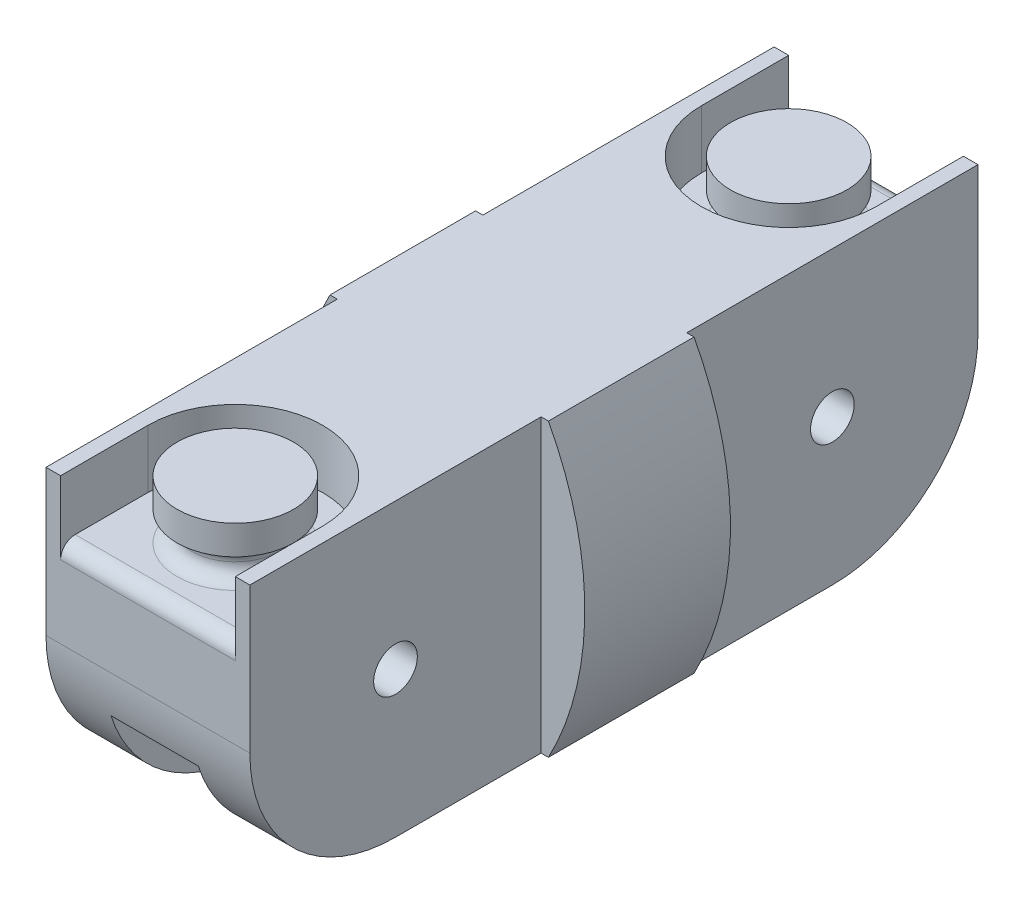
SolidWorks part; units mm, degrees
ref_plane "Alzado" through (0, 0, 0) normal (0, 0, 1) x (1, 0, 0)
ref_plane "Planta" through (0, 0, 0) normal (0, 1, 0) x (1, 0, 0)
ref_plane "Vista lateral" through (0, 0, 0) normal (1, 0, 0) x (0, 0, -1)
sketch "Croquis2" plane through (0, 0, 0) normal (0, 0, 1) x (1, 0, 0)
  line L5 (-7.5, 10) -> (7.5, 10)
  line L7 (-7.5, -10) -> (7.5, -10)
  line L9 (-7.5, 10) -> (7.5, -10) construction
  line L10 (-7.5, -10) -> (7.5, 10) construction
  arc A2 (-7.5, 10) -> (-7.5, -10) centre (11.25, 0) ccw
  arc A3 (7.5, -10) -> (7.5, 10) centre (-11.25, 0) ccw
  point P0 (0, 0)
  dimension "D1" = 15
  dimension "D2" = 20
extrude "Saliente-Extruir1" add sketch "Croquis2" along normal blind 10
sketch "Croquis3" plane through (0, 0, 0) normal (0, 0, -1) x (-1, 0, 0)
  line L0 (7.5, -10) -> (-7.5, -10) construction
  circle A0 centre (0, -7) radius 1.5
  dimension "D2" = 3
  dimension "D1" = 3
extrude "Cortar-Extruir1" cut sketch "Croquis3" against normal blind 10
sketch "Croquis4" plane through (0, 0, 0) normal (0, 0, -1) x (-1, 0, 0)
  line L0 (7.5, -10) -> (-7.5, -10) construction
  line L2 (-7, 10) -> (-7, -10)
  line L3 (-7, -10) -> (-3, -10)
  line L4 (7, 10) -> (7, -10)
  line L5 (-7, 10) -> (7, -10) construction
  line L6 (-7, -10) -> (7, 10) construction
  line L7 (-3, -3) -> (-3, -10)
  line L8 (3, -3) -> (3, -10)
  line L10 (3, -10) -> (7, -10)
  line L11 (-3, -3) -> (3, -3)
  line L13 (-7, 10) -> (7, 10)
  point P0 (0, 0)
  dimension "D1" = 14
  dimension "D2" = 4
  dimension "D3" = 4
  dimension "D4" = 7
extrude "Saliente-Extruir2" add sketch "Croquis4" along normal blind 20
sketch "Croquis5" plane through (0, 0, 10) normal (0, 0, 1) x (1, 0, 0)
  line L0 (-7.5, -10) -> (7.5, -10) construction
  line L2 (-7, 10) -> (-7, -10)
  line L3 (-7, -10) -> (-3, -10)
  line L4 (7, 10) -> (7, -10)
  line L5 (-7, 10) -> (7, -10) construction
  line L6 (-7, -10) -> (7, 10) construction
  line L7 (-3, -3) -> (-3, -10)
  line L8 (3, -3) -> (3, -10)
  line L9 (3, -10) -> (7, -10)
  line L11 (-3, -3) -> (3, -3)
  line L12 (-7, 10) -> (7, 10)
  point P0 (0, 0)
  dimension "D1" = 14
  dimension "D4" = 7
extrude "Saliente-Extruir3" add sketch "Croquis5" along normal blind 20
sketch "Croquis6" plane through (7, 0, 0) normal (1, 0, 0) x (0, 0, -1)
  line L0 (-30, -10) -> (-30, 10) construction
  line L1 (-30, -10) -> (-10, -10) construction
  line L2 (20, 10) -> (20, -10) construction
  circle A0 centre (-20, 0) radius 1.5
  circle A1 centre (10, 0) radius 1.5
  dimension "D3" = 3
  dimension "D6" = 3
  dimension "D1" = 10
  dimension "D2" = 10
  dimension "D4" = 10
extrude "Cortar-Extruir2" cut sketch "Croquis6" against normal blind 14
fillet "Redondeo1" radius 10 4 edges at (5, -10, 30) (-5, -10, 30) (5, -10, -20) (-5, -10, -20)
sketch "Sketch1" plane through (0, 10, 0) normal (0, 1, 0) x (1, 0, 0)
  line L0 (-7, 20) -> (7, 20) construction
  line L1 (7, -30) -> (-7, -30) construction
  line L4 (-6, 14) -> (-6, 20)
  line L5 (-6, 20) -> (6, 20)
  line L6 (6, 14) -> (6, 20)
  line L8 (-6, -24) -> (-6, -30)
  line L9 (-6, -30) -> (6, -30)
  line L10 (6, -24) -> (6, -30)
  arc A0 (-6, 14) -> (6, 14) centre (0, 14) ccw
  arc A1 (6, -24) -> (-6, -24) centre (0, -24) ccw
  dimension "D1" = 12
  dimension "D2" = 12
  dimension "D3" = 6
  dimension "D4" = 6
extrude "Cut-Extrude1" cut sketch "Sketch1" against normal blind 4
sketch "Sketch2" plane through (0, 6, 0) normal (0, 1, 0) x (1, 0, 0)
  line L0 (-6, -30) -> (6, -30) construction
  line L1 (6, 20) -> (-6, 20) construction
  circle A0 centre (0, 14) radius 3
  circle A1 centre (0, -24) radius 3
  dimension "D1" = 6
  dimension "D2" = 6
  dimension "D3" = 6
  dimension "D4" = 6
extrude "Boss-Extrude1" add sketch "Sketch2" along normal blind 2
sketch "Sketch3" plane through (0, 8, 0) normal (0, 1, 0) x (1, 0, 0)
  circle A0 centre (0, -24) radius 4
  circle A1 centre (0, 14) radius 4
  dimension "D1" = 8
  dimension "D2" = 8
extrude "Boss-Extrude2" add sketch "Sketch3" along normal blind 2
fillet "Fillet1" radius 1 4 edges at (0, 8, 27) (0, 6, 27) (0, 8, -11) (0, 6, -11)
fillet "Fillet2" radius 1 2 edges at (0, 6, 30) (0, 6, -20)
fillet "Fillet3" radius 1 2 edges at (-1.5, -7, 0) (-1.5, -7, 10)
